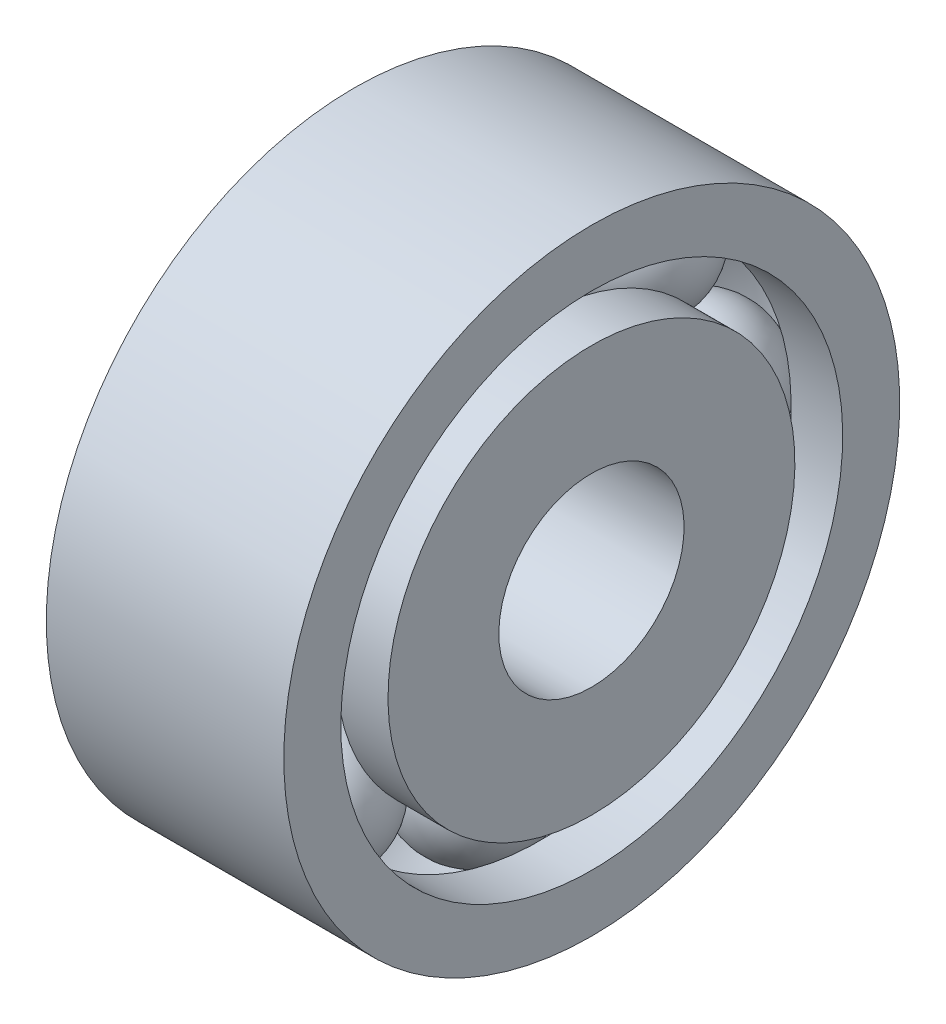
SolidWorks part; units mm, degrees
ref_plane "Front Plane" through (0, 0, 0) normal (0, 0, 1) x (1, 0, 0)
ref_plane "Top Plane" through (0, 0, 0) normal (0, 1, 0) x (1, 0, 0)
ref_plane "Right Plane" through (0, 0, 0) normal (1, 0, 0) x (0, 0, -1)
sketch "Sketch1" plane through (0, 0, 0) normal (0, 0, 1) x (1, 0, 0)
  line L0 (-6.3338, 0) -> (14.2055, 0) construction
  line L1 (-6.3338, 12.1485) -> (-6.3338, 16.4665)
  line L2 (-6.3338, 16.4665) -> (6.3662, 16.4665)
  line L3 (6.3662, 16.4665) -> (6.3662, 12.1485)
  line L4 (-6.3338, 12.1485) -> (6.3662, 12.1485)
  line L5 (-4.8435, 13.4185) -> (-4.8435, 12.1485) construction
  line L6 (-4.8435, 12.1485) -> (-4.8435, 11.4178) construction
  line L7 (-4.8435, 11.4178) -> (-3.7938, 12.1485) construction
  line L8 (-4.8435, 11.4178) -> (-5.8932, 12.1485) construction
  line L9 (0.0162, 15.9585) -> (0.0162, 12.1485) construction
  line L10 (-6.3338, 13.4185) -> (6.3662, 13.4185)
  line L11 (0.0162, 12.1485) -> (0, 0) construction
  circle A1 centre (0.0162, 12.1485) radius 3.81
  spline S0 degree 2 poles (-3.7938, 12.1485) (-4.8435, 14.6885) (-5.8932, 12.1485) knots 0 0 0 1 1 1
  spline S1 degree 2 poles (3.8262, 12.1485) (4.876, 14.6885) (5.9257, 12.1485) knots 0 0 0 1 1 1
  point P6 (3.9359, 0)
  dimension "D1" = 7.62
  dimension "D2" = 12.7
  dimension "D4" = 12.1485
  dimension "D5" = 1.27
  dimension "D6" = 4.318
revolve "Revolve1" add sketch "Sketch1" angle 360 about L0 region at (-6.2032, 14.9425, 0) reverse direction yes
sketch "Sketch4" plane through (0, 0, 0) normal (0, 0, 1) x (1, 0, 0)
  line L3 (-6.35, 4.953) -> (-6.35, 10.8785)
  line L5 (6.35, 10.8785) -> (6.35, 4.953)
  line L6 (0, 12.1485) -> (0, 0) construction
  line L7 (6.35, 0) -> (-6.35, 0) construction
  line L9 (-6.35, 4.953) -> (6.35, 4.953)
  line L12 (-6.35, 10.8785) -> (6.35, 10.8785)
  line L13 (-6.35, 10.8785) -> (-6.35, 4.953)
  line L21 (6.35, 10.8785) -> (6.35, 4.953)
  circle A1 centre (0, 12.1485) radius 3.81
  point P0 (0, 0)
  point P13 (0, 0)
  dimension "D3" = 7.62
  dimension "D1" = 12.1485
  dimension "D2" = 1.27
  dimension "D4" = 4.953
  dimension "D5" = 5.9255
  dimension "D7" = 12.7
revolve "Revolve2" add sketch "Sketch4" angle 360 about L7 region at (0, 7.5053, 0) reverse direction yes
sketch "Sketch5" plane through (0, 0, 0) normal (0, 0, 1) x (1, 0, 0)
  line L0 (0, 0) -> (0, 12.1485) construction
  line L2 (0, 8.529) -> (0, 15.768)
  arc A0 (0, 8.529) -> (0, 15.768) centre (0, 12.1485) ccw
  dimension "D2" = 7.239
  dimension "D1" = 12.1485
revolve "Revolve5" add sketch "Sketch5" angle 360 about L0
pattern_circular "CirPattern2" count 8 over 360 about axis through (6.35, 0, 0) along (-1, 0, 0) of bodies 104
